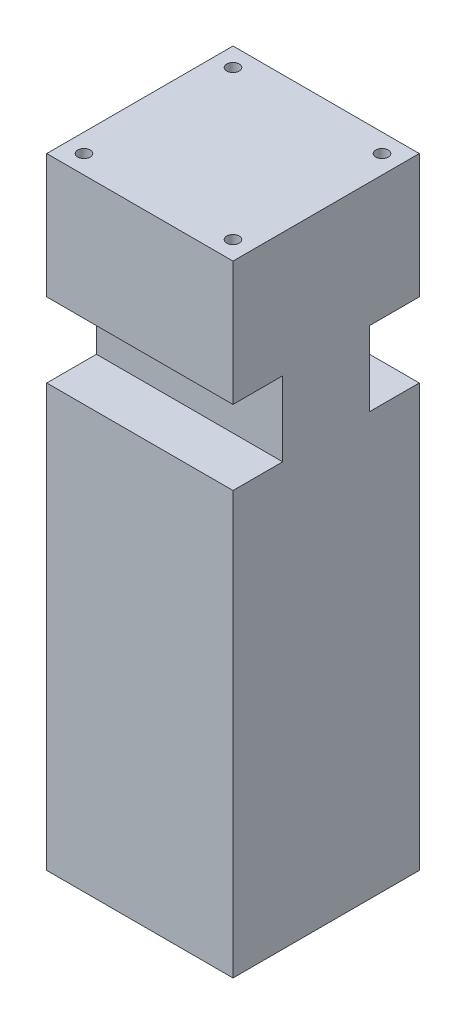
SolidWorks part; units mm, degrees
ref_plane "Front Plane" through (0, 0, 0) normal (0, 0, 1) x (1, 0, 0)
ref_plane "Top Plane" through (0, 0, 0) normal (0, 1, 0) x (1, 0, 0)
ref_plane "Right Plane" through (0, 0, 0) normal (1, 0, 0) x (0, 0, -1)
sketch "Sketch2" plane through (0, 0, 0) normal (0, 1, 0) x (1, 0, 0)
  line L1 (0, 0) -> (150, 0)
  line L2 (0, 0) -> (0, 150)
  line L3 (0, 150) -> (150, 150)
  line L4 (150, 0) -> (150, 150)
  dimension "D1" = 150
  dimension "D2" = 150
extrude "Boss-Extrude1" add sketch "Sketch2" along normal blind 500
sketch "Sketch4" plane through (150, 0, 0) normal (1, 0, 0) x (0, 0, -1)
  line L0 (0, 500) -> (0, 400)
  line L1 (0, 500) -> (0, 0) construction
  line L2 (0, 400) -> (40, 400)
  line L3 (40, 400) -> (40, 340)
  line L4 (40, 340) -> (0, 340)
  line L5 (0, 400) -> (0, 340)
  point P5 (40, 370)
  line M6 (0, 500) -> (0, 0)
  dimension "D1" = 30
  dimension "D2" = 40
  dimension "D3" = 100
extrude "Cut-Extrude1" cut sketch "Sketch4" against normal through all both and the other way through all contours L4 L3 L2 M6 region at (150, 370, -20)
sketch "Sketch5" plane through (0, 500, 0) normal (0, 1, 0) x (1, 0, 0)
  line L1 (0, 0) -> (15, 0)
  line L2 (0, 0) -> (0, 15)
  line L3 (0, 15) -> (10, 15)
  line L4 (15, 0) -> (15, 10)
  line L5 (150, 0) -> (135, 0)
  line L6 (150, 0) -> (150, 15)
  line L7 (150, 15) -> (140, 15)
  line L8 (135, 0) -> (135, 10)
  circle A0 centre (15, 15) radius 5
  circle A1 centre (135, 15) radius 5
  dimension "D3" = 10
  dimension "D6" = 10
  dimension "D1" = 15
  dimension "D2" = 15
  dimension "D4" = 15
  dimension "D5" = 15
extrude "Cut-Extrude2" cut sketch "Sketch5" against normal blind 150 contours A0 | A1 L4 region at (15, 500, -15) region at (135, 500, -15)
ref_plane "Plane1" through (0, 0, -75) normal (0, 0, -1) x (-1, 0, 0)
mirror "Mirror2" about plane through (0, 0, -75) normal (0, 0, -1) of "Cut-Extrude1", "Cut-Extrude2"
